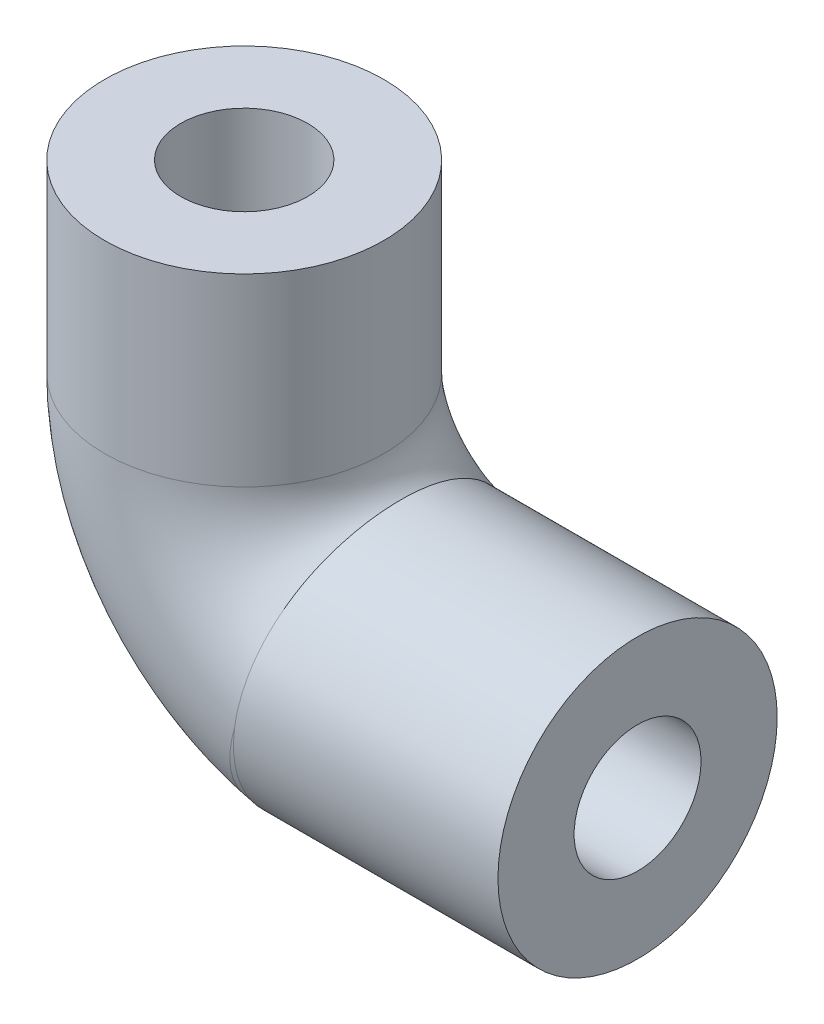
SolidWorks part; units mm, degrees
ref_plane "Front Plane" through (0, 0, 0) normal (0, 0, 1) x (1, 0, 0)
ref_plane "Top Plane" through (0, 0, 0) normal (0, 1, 0) x (1, 0, 0)
ref_plane "Right Plane" through (0, 0, 0) normal (1, 0, 0) x (0, 0, -1)
sketch "Sketch1" plane through (0, 0, 0) normal (0, 0, 1) x (1, 0, 0)
  line L0 (-18.6064, 18.4633) -> (-18.6064, 0)
  line L1 (-5.5819, -17.1322) -> (20.7533, -17.1322)
  arc A0 (-18.6064, 0) -> (-5.5819, -17.1322) centre (-0.8264, 0) ccw
  dimension "D1" = 17.78
ref_plane "Plane1" through (20.7533, -17.1322, 0) normal (1, 0, 0) x (0, 0, -1)
sketch "Sketch2" plane through (20.7533, -17.1322, 0) normal (1, 0, 0) x (0, 0, -1)
  circle A0 centre (0, 0) radius 13.97
  circle A1 centre (0, 0) radius 6.35
  dimension "D1" = 27.94
  dimension "D2" = 12.7
sweep "Sweep1" add profiles "Sketch2" path "Sketch1"
